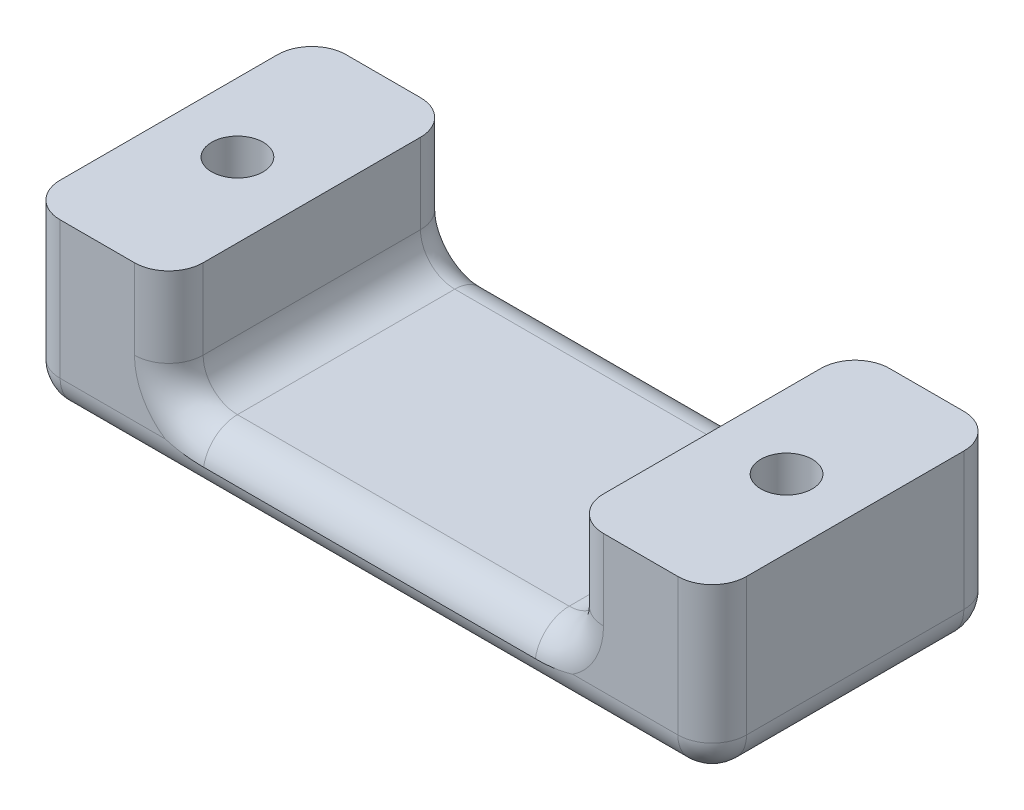
SolidWorks part; units mm, degrees
ref_plane "Front Plane" through (0, 0, 0) normal (0, 0, 1) x (1, 0, 0)
ref_plane "Top Plane" through (0, 0, 0) normal (0, 1, 0) x (1, 0, 0)
ref_plane "Right Plane" through (0, 0, 0) normal (1, 0, 0) x (0, 0, -1)
sketch "Sketch1" plane through (0, 0, 0) normal (0, 1, 0) x (1, 0, 0)
  line L1 (0, 0) -> (60, 0)
  line L2 (0, 0) -> (0, 25)
  line L3 (0, 25) -> (60, 25)
  line L4 (60, 0) -> (60, 25)
  dimension "D1" = 60
  dimension "D2" = 25
extrude "Boss-Extrude1" add sketch "Sketch1" along normal blind 5
sketch "Sketch2" plane through (0, 5, 0) normal (0, 1, 0) x (1, 0, 0)
  line L0 (0, 0) -> (60, 0) construction
  line L1 (0, 25) -> (12.5, 25)
  line L2 (0, 25) -> (0, 0)
  line L3 (0, 0) -> (12.5, 0)
  line L4 (12.5, 25) -> (12.5, 0)
  line L6 (60, 25) -> (47.5, 25)
  line L7 (60, 25) -> (60, 0)
  line L8 (60, 0) -> (47.5, 0)
  line L9 (47.5, 25) -> (47.5, 0)
  dimension "D1" = 35
extrude "Boss-Extrude2" add sketch "Sketch2" along normal blind 10
sketch "Sketch3" plane through (0, 0, 0) normal (0, -1, 0) x (1, 0, 0)
  line L0 (0, -12.5) -> (60, -12.5) construction
  line L1 (0, -25) -> (0, 0) construction
  line L2 (60, 0) -> (60, -25) construction
  line L3 (30, 0) -> (30, -25) construction
  line L4 (0, 0) -> (60, 0) construction
  line L5 (60, -25) -> (0, -25) construction
  circle A0 centre (6, -12.5) radius 2.25
  circle A2 centre (54, -12.5) radius 2.25
  dimension "D1" = 4.5
  dimension "D2" = 48
extrude "Cut-Extrude1" cut sketch "Sketch3" against normal blind 15
fillet "Fillet1" radius 3 16 edges at (12.5, 10, 0) (47.5, 10, 0) (47.5, 10, -25) (12.5, 10, -25) (60, 7.5, -25) (60, 7.5, 0) (0, 7.5, 0) (0, 7.5, -25) (30, 5, 0) (30, 5, -25) (47.5, 5, -12.5) (12.5, 5, -12.5) (30, 0, 0) (30, 0, -25) (60, 0, -12.5) (0, 0, -12.5)
